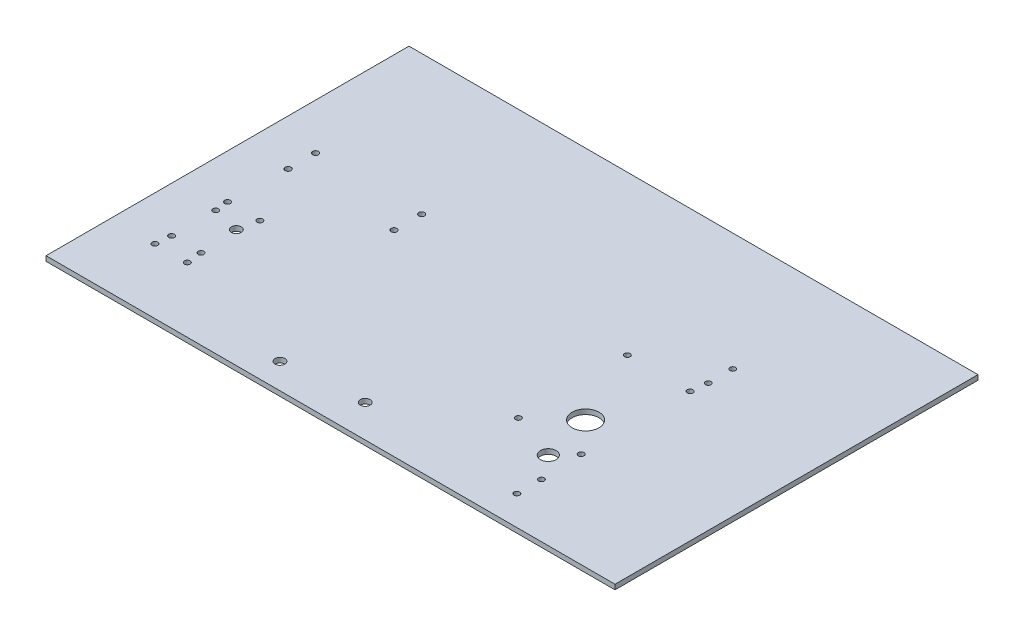
SolidWorks part; units mm, degrees
ref_plane "Front Plane" through (0, 0, 0) normal (0, 0, 1) x (1, 0, 0)
ref_plane "Top Plane" through (0, 0, 0) normal (0, 1, 0) x (1, 0, 0)
ref_plane "Right Plane" through (0, 0, 0) normal (1, 0, 0) x (0, 0, -1)
sketch "Sketch1" plane through (0, 0, 0) normal (0, 1, 0) x (1, 0, 0)
  line L1 (-158.75, 88.9) -> (158.75, 88.9)
  line L2 (-158.75, 88.9) -> (-158.75, -88.9)
  line L3 (-158.75, -88.9) -> (158.75, -88.9)
  line L4 (158.75, 88.9) -> (158.75, -88.9)
  line L5 (-158.75, 88.9) -> (158.75, -88.9) construction
  line L6 (-158.75, -88.9) -> (158.75, 88.9) construction
  circle A0 centre (-111.76, -12.7) radius 3.175
  circle A1 centre (107.95, -6.35) radius 8.7313
  circle A4 centre (-129.032, 55.88) radius 1.905
  circle A5 centre (-60.452, 55.88) radius 1.905
  circle A7 centre (-129.032, 38.1) radius 1.905
  circle A8 centre (-60.452, 38.1) radius 1.905
  point P0 (0, 0)
  dimension "D3" = 6.35
  dimension "D4" = 17.4625
  dimension "D14" = 3.81
  dimension "D17" = 17.78
  dimension "D1" = 317.5
  dimension "D2" = 177.8
  dimension "D5" = 46.99
  dimension "D6" = 266.7
  dimension "D7" = 95.25
  dimension "D8" = 76.2
  dimension "D13" = 29.718
  dimension "D15" = 68.58
  dimension "D16" = 127
extrude "Boss-Extrude1" add sketch "Sketch1" along normal blind 3.175
sketch "Sketch2" plane through (0, 3.175, 0) normal (0, 1, 0) x (1, 0, 0)
  line L0 (-158.75, 88.9) -> (-158.75, -88.9) construction
  line L1 (-158.75, -88.9) -> (158.75, -88.9) construction
  circle A0 centre (-89.0817, -33.177) radius 1.905
  circle A1 centre (-132.1376, -36.4483) radius 1.905
  dimension "D1" = 3.81
  dimension "D2" = 69.6683
  dimension "D3" = 52.4517
  dimension "D4" = 55.723
  dimension "D5" = 43.18
extrude "Cut-Extrude1" [suppressed] cut sketch "Sketch2" against normal through all
sketch "Sketch3" plane through (0, 0, 0) normal (0, -1, 0) x (-1, 0, 0)
  line L0 (158.75, -88.9) -> (-158.75, -88.9) construction
  line L1 (158.75, 88.9) -> (158.75, -88.9) construction
  circle A0 centre (23.8295, -72.39) radius 3.175
  circle A1 centre (-26.7643, -67.818) radius 3.175
  dimension "D1" = 6.35
  dimension "D2" = 4.572
  dimension "D3" = 16.51
  dimension "D4" = 185.5143
  dimension "D5" = 50.8
extrude "Cut-Extrude2" cut sketch "Sketch3" against normal through all
sketch "Sketch4" plane through (0, 3.175, 0) normal (0, 1, 0) x (1, 0, 0)
  line L0 (-158.75, -88.9) -> (158.75, -88.9) construction
  line L1 (158.75, 88.9) -> (133.35, 88.9)
  line L2 (158.75, 88.9) -> (158.75, -88.9)
  line L3 (158.75, -88.9) -> (133.35, -88.9)
  line L4 (133.35, 88.9) -> (133.35, -88.9)
  dimension "D1" = 25.4
extrude "Cut-Extrude3" cut sketch "Sketch4" against normal through all
sketch "Sketch5" plane through (0, 3.175, 0) normal (0, 1, 0) x (1, 0, 0)
  line L0 (133.35, 88.9) -> (-158.75, 88.9) construction
  line L1 (133.35, 88.9) -> (133.35, -88.9) construction
  circle A0 centre (115.57, -38.1) radius 5.08
  dimension "D3" = 10.16
  dimension "D1" = 127
  dimension "D2" = 17.78
extrude "Cut-Extrude4" cut sketch "Sketch5" against normal through all
sketch "Sketch6" plane through (0, 0, 0) normal (0, -1, 0) x (1, 0, 0)
  line L0 (-158.75, 88.9) -> (133.35, 88.9) construction
  line L1 (133.35, -88.9) -> (133.35, 88.9) construction
  line L2 (133.35, -88.9) -> (-158.75, -88.9) construction
  circle A0 centre (127, 69.85) radius 1.8034
  circle A2 centre (127, 53.975) radius 1.8034
  circle A3 centre (127, -53.975) radius 1.8034
  circle A4 centre (127, -69.85) radius 1.8034
  dimension "D4" = 3.6068
  dimension "D5" = 6.35
  dimension "D1" = 15.875
  dimension "D2" = 19.05
  dimension "D3" = 6.35
  dimension "D6" = 15.875
  dimension "D7" = 19.05
extrude "Cut-Extrude5" cut sketch "Sketch6" against normal through all
sketch "Sketch7" plane through (0, 3.175, 0) normal (0, 1, 0) x (1, 0, 0)
  line L0 (133.35, 88.9) -> (133.35, -88.9) construction
  line L1 (133.35, 88.9) -> (-158.75, 88.9) construction
  line L2 (-158.75, 88.9) -> (-158.75, -88.9) construction
  line L3 (-158.75, -88.9) -> (133.35, -88.9) construction
  circle A1 centre (125.73, 43.4975) radius 1.8415
  circle A2 centre (85.09, 43.4975) radius 1.8415
  circle A3 centre (85.09, -26.9875) radius 1.8415
  circle A4 centre (125.73, -26.9875) radius 1.8415
  circle A5 centre (-130.175, -46.99) radius 1.8415
  circle A6 centre (-109.22, -46.99) radius 1.8415
  circle A7 centre (-129.2225, -37.1475) radius 1.8415
  circle A8 centre (-110.1725, -37.1475) radius 1.8415
  circle A9 centre (-129.2225, -8.5725) radius 1.8415
  circle A10 centre (-130.175, 0) radius 1.8415
  circle A11 centre (-109.22, 0) radius 1.8415
  dimension "D1" = 7.62
  dimension "D5" = 3.683
  dimension "D10" = 3.683
  dimension "D15" = 3.683
  dimension "D2" = 40.64
  dimension "D3" = 70.485
  dimension "D4" = 61.9125
  dimension "D6" = 28.575
  dimension "D7" = 20.955
  dimension "D8" = 0.9525
  dimension "D9" = 19.05
  dimension "D11" = 88.9
  dimension "D12" = 8.5725
  dimension "D13" = 28.575
  dimension "D14" = 9.8425
extrude "Cut-Extrude6" cut sketch "Sketch7" against normal through all
sketch "Sketch8" plane through (0, 0, 0) normal (0, -1, 0) x (1, 0, 0)
  line L1 (-158.75, -88.9) -> (-158.75, 88.9) construction
  line L2 (-158.75, 88.9) -> (133.35, 88.9) construction
  line L3 (133.35, 88.9) -> (133.35, -88.9)
  line L4 (133.35, -88.9) -> (-158.75, -88.9) construction
  line L5 (133.35, -88.9) -> (-158.75, -88.9)
  line L6 (-158.75, -88.9) -> (-158.75, -146.05)
  line L7 (-158.75, -146.05) -> (209.55, -146.05)
  line L8 (209.55, -146.05) -> (209.55, 88.9)
  line L9 (209.55, 88.9) -> (133.35, 88.9)
  line L12 (133.35, -88.9) -> (133.35, 88.9) construction
  point P0 (209.55, -145.2409)
  point P13 (242.7872, -146.05)
  point P14 (142.6136, 96.8322)
  point P15 (-158.75, -88.9)
  point P16 (147.1467, 88.9)
  point P17 (133.35, -88.9)
  dimension "D1" = 76.2
  dimension "D2" = 57.15
extrude "Boss-Extrude2" add sketch "Sketch8" against normal through all
